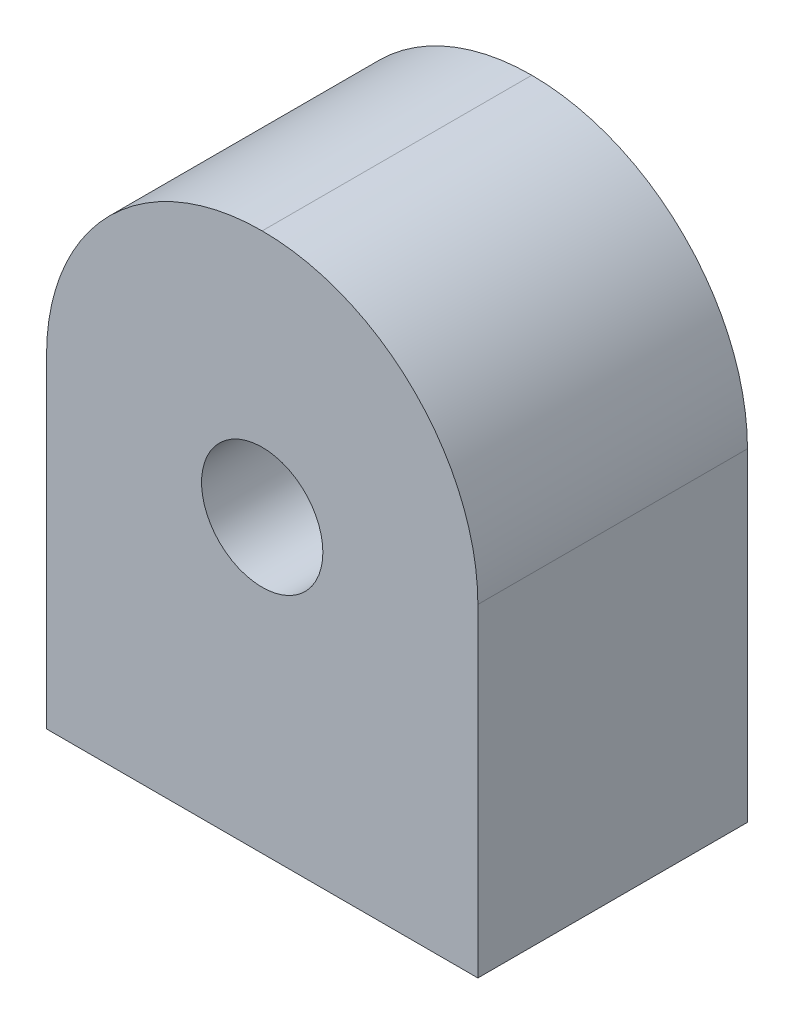
SolidWorks part; units mm, degrees
ref_plane "Front Plane" through (0, 0, 0) normal (0, 0, 1) x (1, 0, 0)
ref_plane "Top Plane" through (0, 0, 0) normal (0, 1, 0) x (1, 0, 0)
ref_plane "Right Plane" through (0, 0, 0) normal (1, 0, 0) x (0, 0, -1)
sketch "Sketch1" plane through (0, 0, 0) normal (0, 0, 1) x (1, 0, 0)
  line L1 (0, 0) -> (16, 0)
  line L2 (0, 0) -> (0, 20)
  line L3 (0, 20) -> (16, 20)
  line L4 (16, 0) -> (16, 20)
  dimension "D1" = 16
  dimension "D2" = 20
extrude "Boss-Extrude1" add sketch "Sketch1" along normal blind 10
sketch "Sketch2" plane through (0, 0, 10) normal (0, 0, 1) x (1, 0, 0)
  line L0 (8, 0) -> (8, 20) construction
  line L1 (0, 0) -> (16, 0) construction
  line L2 (16, 20) -> (0, 20) construction
  circle A0 centre (8, 10.8) radius 2.25
  dimension "D1" = 4.5
  dimension "D2" = 10.8
extrude "Cut-Extrude1" cut sketch "Sketch2" against normal through all
fillet "Fillet1" radius 8 2 edges at (16, 20, 5) (0, 20, 5)
